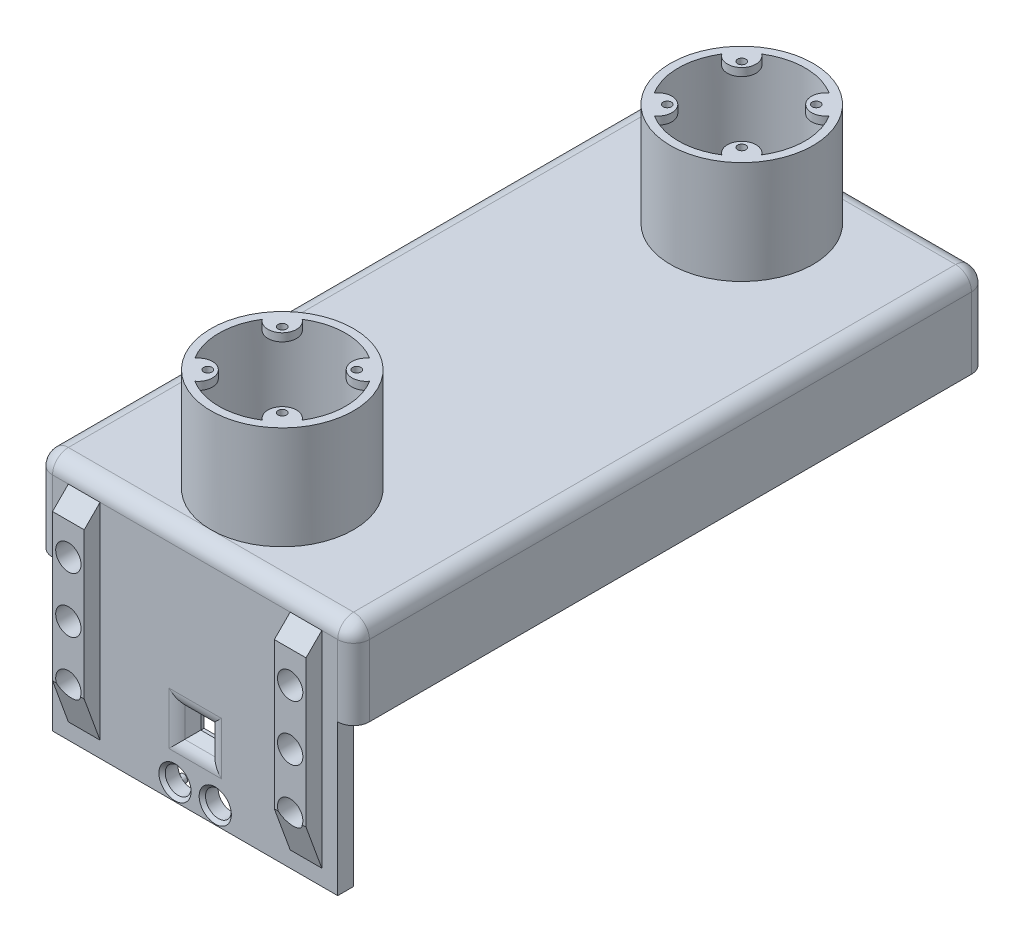
SolidWorks part; units mm, degrees
ref_plane "Front Plane" through (0, 0, 0) normal (0, 0, 1) x (1, 0, 0)
ref_plane "Top Plane" through (0, 0, 0) normal (0, 1, 0) x (1, 0, 0)
ref_plane "Right Plane" through (0, 0, 0) normal (1, 0, 0) x (0, 0, -1)
sketch "Sketch1" plane through (0, 0, 0) normal (0, 0, 1) x (1, 0, 0)
  line L1 (-90, -75) -> (90, -75)
  line L2 (-90, -75) -> (-90, 75)
  line L3 (-90, 75) -> (90, 75)
  line L4 (90, -75) -> (90, 75)
  line L5 (-90, -75) -> (90, 75) construction
  line L6 (-90, 75) -> (90, -75) construction
  point P0 (0, 0)
  dimension "D1" = 150
  dimension "D2" = 180
extrude "Boss-Extrude1" add sketch "Sketch1" along normal blind 10
sketch "Sketch2" plane through (0, 0, 10) normal (0, 0, 1) x (1, 0, 0)
  line L0 (0, 0) -> (0, 75) construction
  line L1 (90, 75) -> (-90, 75) construction
  line L2 (0, 0) -> (-70, 0) construction
  line L3 (80, 65) -> (60, 65)
  line L4 (-80, -65) -> (-60, -65)
  line L5 (-80, -65) -> (-80, 65)
  line L6 (-80, 65) -> (-60, 65)
  line L7 (-60, -65) -> (-60, 65)
  line L8 (-80, -65) -> (-60, 65) construction
  line L9 (-80, 65) -> (-60, -65) construction
  line L10 (60, -65) -> (60, 65)
  line L11 (80, -65) -> (60, -65)
  line L12 (80, -65) -> (80, 65)
  dimension "D1" = 130
  dimension "D2" = 20
extrude "Boss-Extrude2" add sketch "Sketch2" along normal blind 10
sketch "Sketch3" plane through (0, 0, 20) normal (0, 0, 1) x (1, 0, 0)
  line L0 (-70, 65) -> (-70, -65) construction
  line L1 (-60, 65) -> (-80, 65) construction
  line L2 (-80, -65) -> (-60, -65) construction
  line L3 (-70, 0) -> (-70, -35) construction
  line L4 (-70, 0) -> (-70, 35) construction
  line L5 (0, 0) -> (0, 46.7529) construction
  circle A0 centre (-70, 0) radius 8
  circle A1 centre (-70, -35) radius 8
  circle A2 centre (-70, 35) radius 8
  circle A3 centre (70, -35) radius 8
  circle A4 centre (70, 0) radius 8
  circle A5 centre (70, 35) radius 8
extrude "Cut-Extrude1" cut sketch "Sketch3" against normal up to next
chamfer "Chamfer1" distance 10 angle 45 2 edges at (70, 65, 20) (-70, 65, 20)
chamfer "Chamfer2" distance 10 angle 70 2 edges at (70, -65, 20) (-70, -65, 20) first distance on face at (70, -65, 15) first distance on face at (-70, -65, 15)
sketch "Sketch5" plane through (0, 75, 0) normal (0, 1, 0) x (1, 0, 0)
  line L1 (100, -10) -> (-100, -10)
  line L3 (100, 390) -> (-100, 390)
  line L4 (-100, -10) -> (-100, 390)
  line L5 (100, -10) -> (100, 390)
  dimension "D2" = 400
extrude "Boss-Extrude4" add sketch "Sketch5" against normal blind 10
sketch "Sketch6" plane through (0, 0, -390) normal (0, 0, -1) x (-1, 0, 0)
  line L1 (-100, 75) -> (100, 75)
  line L2 (-100, 75) -> (-100, 20)
  line L3 (-100, 20) -> (100, 20)
  line L4 (100, 75) -> (100, 20)
  dimension "D1" = 200
  dimension "D2" = 55
extrude "Boss-Extrude5" add sketch "Sketch6" against normal blind 10
sketch "Sketch7" plane through (0, 65, 0) normal (0, -1, 0) x (1, 0, 0)
  line L0 (100, -390) -> (-100, -390) construction
  line L1 (-100, 10) -> (-90, 10)
  line L2 (-100, 10) -> (-100, -390)
  line L3 (-100, -390) -> (-90, -390)
  line L4 (-90, 10) -> (-90, -390)
  line L5 (-90, 10) -> (90, 10) construction
  line L6 (100, -390) -> (90, -390)
  line L7 (100, -390) -> (100, 10)
  line L8 (100, 10) -> (90, 10)
  line L9 (90, -390) -> (90, 10)
extrude "Boss-Extrude6" add sketch "Sketch7" along normal blind 45
fillet "Fillet1" radius 10 8 edges at (-100, 75, -190) (100, 75, -190) (0, 75, -390) (0, 75, 10) (100, 47.5, 10) (100, 47.5, -390) (-100, 47.5, -390) (-100, 47.5, 10)
sketch "Sketch8" plane through (0, 75, 0) normal (0, 1, 0) x (1, 0, 0)
  line L0 (-90, 190) -> (90, 190) construction
  line L1 (-90, 380) -> (-90, 0) construction
  line L2 (90, 0) -> (90, 380) construction
  line L3 (0, 390) -> (0, 335) construction
  line L4 (-100, -10) -> (100, -10) construction
  line L5 (-100, -10) -> (-100, 390) construction
  line L6 (-100, 390) -> (100, 390) construction
  line L7 (100, -10) -> (100, 390) construction
  line L8 (-100, -10) -> (100, 390) construction
  line L9 (-100, 390) -> (100, -10) construction
  line L10 (-100, 65) -> (100, 65) construction
  line L11 (-100, 65) -> (-100, 315) construction
  line L12 (-100, 315) -> (100, 315) construction
  line L13 (100, 65) -> (100, 315) construction
  line L14 (-100, 65) -> (100, 315) construction
  line L15 (-100, 315) -> (100, 65) construction
  line L16 (0, -10) -> (0, 45) construction
  circle A2 centre (0, 335) radius 40
  circle A3 centre (0, 45) radius 40
  point P6 (0, 190)
  point P11 (0, 190)
  dimension "D1" = 250
sketch "Sketch9" plane through (0, 75, 0) normal (0, 1, 0) x (1, 0, 0)
  line L0 (0, -10) -> (0, 45) construction
  line L1 (0, 390) -> (0, 335) construction
  line L2 (0, -10) -> (0, 45) construction
  line L3 (0, 390) -> (0, 335) construction
  circle A0 centre (0, 45) radius 40 construction
  circle A1 centre (0, 335) radius 40 construction
  circle A2 centre (0, 45) radius 40
  circle A3 centre (0, 335) radius 40
extrude "Cut-Extrude2" cut sketch "Sketch9" against normal blind 10
sketch "Sketch10" plane through (-90, 0, 0) normal (1, 0, 0) x (0, 0, -1)
  line L0 (0, 65) -> (0, 20) construction
  line L1 (380, 20) -> (0, 20)
  line L2 (380, 20) -> (380, 30)
  line L3 (380, 30) -> (0, 30)
  line L4 (0, 20) -> (0, 30)
  dimension "D1" = 10
extrude "Boss-Extrude7" add sketch "Sketch10" along normal blind 180
sketch "Sketch11" plane through (0, 20, 0) normal (0, -1, 0) x (1, 0, 0)
  line L2 (0, -45) -> (0, -90) construction
  line L3 (0, -335) -> (0, -290) construction
  line L5 (-100, 10) -> (-100, -390) construction
  line L6 (100, 10) -> (100, -390) construction
  line L8 (100, -90) -> (-100, -90)
  line L11 (-90, 0) -> (-60, 0)
  line L12 (-90, 0) -> (-90, -20)
  line L13 (-90, -20) -> (-60, -20)
  line L14 (-60, 0) -> (-60, -20)
  line L15 (90, -20) -> (60, -20)
  line L16 (60, 0) -> (60, -20)
  line L17 (90, 0) -> (60, 0)
  line L18 (90, 0) -> (90, -20)
  line L20 (-90, -290) -> (90, -290)
  line L21 (-90, -290) -> (-90, -90)
  line L22 (-90, -90) -> (90, -90)
  line L23 (90, -290) -> (90, -90)
  line L24 (-90, -290) -> (90, -90) construction
  line L25 (-90, -90) -> (90, -290) construction
  circle A0 centre (0, -45) radius 40 construction
  circle A1 centre (0, -335) radius 40 construction
  point P26 (0, -190)
  line M12 (90, 0) -> (-90, 0)
  dimension "D1" = 20
  dimension "D2" = 30
extrude "Cut-Extrude5" cut sketch "Sketch11" against normal blind 10 contours L20 L23 L8 L21 | L14 L12 L13 M12 | L18 L16 L15 M12 region at (0, 20, -190) region at (75, 20, -10) region at (-75, 20, -10)
sketch "Sketch13" plane through (0, 75, 0) normal (0, 1, 0) x (1, 0, 0)
  line L0 (-90, 190) -> (90, 190) construction
  circle A0 centre (0, 45) radius 40
  circle A1 centre (0, 45) radius 45
  circle A2 centre (0, 335) radius 40
  circle A3 centre (0, 335) radius 45
extrude "Boss-Extrude8" add sketch "Sketch13" along normal blind 60
sketch "Sketch14" plane through (0, 135, 0) normal (0, 1, 0) x (1, 0, 0)
  line L0 (0, 335) -> (0, 358.5) construction
  line L1 (0, 390) -> (0, 335) construction
  line L2 (0, 358.5) -> (-23.5, 358.5) construction
  line L3 (0, 335) -> (-25.7533, 335) construction
  line L4 (100, 190) -> (-100, 190) construction
  line L5 (100, -10) -> (100, 390) construction
  line L6 (-100, -10) -> (-100, 390) construction
  line L7 (-23.5, 358.5) -> (-23.5, 366.0195) construction
  line L8 (-23.5, 358.5) -> (-26.5406, 361.5406) construction
  circle A2 centre (-23.5, 358.5) radius 2.6
  circle A3 centre (23.5, 358.5) radius 2.6
  circle A4 centre (23.5, 311.5) radius 2.6
  circle A5 centre (-23.5, 311.5) radius 2.6
  circle A6 centre (-23.5, 68.5) radius 2.6
  circle A7 centre (23.5, 68.5) radius 2.6
  circle A8 centre (23.5, 21.5) radius 2.6
  circle A9 centre (-23.5, 21.5) radius 2.6
  arc A10 (-33.8573, 356.2998) -> (-21.2998, 368.8573) centre (-26.5406, 361.5406) ccw
  circle A11 centre (0, 335) radius 45
  arc A12 (-33.8573, 356.2998) -> (-33.8573, 313.7002) centre (0, 335) ccw
  arc A13 (33.8573, 356.2998) -> (21.2998, 368.8573) centre (26.5406, 361.5406) cw
  arc A14 (-33.8573, 313.7002) -> (-21.2998, 301.1427) centre (-26.5406, 308.4594) cw
  arc A15 (33.8573, 313.7002) -> (21.2998, 301.1427) centre (26.5406, 308.4594) ccw
  circle A16 centre (0, 45) radius 45
  arc A17 (-33.8573, 23.7002) -> (-33.8573, 66.2998) centre (0, 45) cw
  arc A18 (-33.8573, 66.2998) -> (-21.2998, 78.8573) centre (-26.5406, 71.5406) ccw
  arc A19 (33.8573, 66.2998) -> (21.2998, 78.8573) centre (26.5406, 71.5406) cw
  arc A20 (33.8573, 23.7002) -> (21.2998, 11.1427) centre (26.5406, 18.4594) ccw
  arc A21 (-33.8573, 23.7002) -> (-21.2998, 11.1427) centre (-26.5406, 18.4594) cw
  arc A22 (-21.2998, 78.8573) -> (21.2998, 78.8573) centre (0, 45) cw
  arc A23 (33.8573, 66.2998) -> (33.8573, 23.7002) centre (0, 45) cw
  arc A24 (21.2998, 11.1427) -> (-21.2998, 11.1427) centre (0, 45) cw
  arc A25 (33.8573, 313.7002) -> (33.8573, 356.2998) centre (0, 335) ccw
  arc A26 (-21.2998, 301.1427) -> (21.2998, 301.1427) centre (0, 335) ccw
  arc A27 (21.2998, 368.8573) -> (-21.2998, 368.8573) centre (0, 335) ccw
  dimension "D1" = 45
  dimension "D2" = 4.3
extrude "Boss-Extrude9" add sketch "Sketch14" along normal blind 5
sketch "Sketch15" plane through (-100, 0, 0) normal (-1, 0, 0) x (0, 0, 1)
  line L0 (-190, 75) -> (-190, 275) construction
sketch "Sketch16" plane through (0, 140, 0) normal (0, 1, 0) x (1, 0, 0)
  line L0 (0, 290) -> (0, 90) construction
  circle A0 centre (0, 335) radius 45 construction
  circle A1 centre (0, 335) radius 45 construction
  circle A2 centre (0, 45) radius 45 construction
  circle A3 centre (0, 45) radius 45 construction
sketch "Sketch17" plane through (0, 0, 0) normal (0, 0, -1) x (-1, 0, 0)
  line L0 (0, -75) -> (0, -64.35) construction
  line L1 (90, -75) -> (-90, -75) construction
  line L3 (-22.85, -53.7) -> (22.85, -53.7) construction
  line L4 (-22.85, -53.7) -> (-22.85, -75) construction
  line L5 (-22.85, -75) -> (22.85, -75) construction
  line L6 (22.85, -53.7) -> (22.85, -75) construction
  line L7 (-22.85, -53.7) -> (22.85, -75) construction
  line L8 (-22.85, -75) -> (22.85, -53.7) construction
  circle A0 centre (-20.35, -56.2) radius 1.5
  circle A1 centre (20.35, -72.5) radius 1.5
  circle A2 centre (-20.35, -56.2) radius 2.5
  circle A3 centre (20.35, -72.5) radius 2.5
  dimension "D1" = 2.5
  dimension "D3" = 3
  dimension "D6" = 3
  dimension "D2" = 2.5
  dimension "D4" = 2.5
  dimension "D5" = 2.5
extrude "Boss-Extrude10" add sketch "Sketch17" along normal blind 3
sketch "Sketch18" plane through (0, 0, 0) normal (0, 0, -1) x (-1, 0, 0)
  line L0 (0, -75) -> (0, -53.7) construction
  line L1 (20.35, -75) -> (-90, -75) construction
  line L3 (0, -64.35) -> (-20.85, -64.35) construction
  circle A0 centre (-12.7, -64.35) radius 8.15
  circle A1 centre (12.7, -64.35) radius 8.15
  point P10 (0, 0)
  dimension "D1" = 20.85
extrude "Cut-Extrude6" cut sketch "Sketch18" against normal through all
chamfer "Chamfer3" distance 2 angle 45 2 edges at (4.55, -64.35, 10) (-20.85, -64.35, 10)
sketch "Sketch19" plane through (0, 0, 10) normal (0, 0, 1) x (1, 0, 0)
  line L0 (0, -75) -> (0, -45) construction
  line L1 (-90, -75) -> (90, -75) construction
  line L2 (0, -45) -> (0, -21) construction
  line L3 (-10.5, -43.2) -> (-10.5, -37.05) construction
  line L4 (-12.6, -45) -> (12.6, -45)
  line L5 (-12.6, -45) -> (-12.6, -21)
  line L6 (-12.6, -21) -> (12.6, -21) construction
  line L7 (12.6, -45) -> (12.6, -21)
  line L8 (-12.6, -45) -> (12.6, -21) construction
  line L9 (-12.6, -21) -> (12.6, -45) construction
  line L10 (-10.5, -37.05) -> (3.3057, -37.05) construction
  circle A1 centre (-10.5, -43.2) radius 1.05
  circle A2 centre (10.5, -43.2) radius 1.05
  circle A7 centre (10.5, -43.2) radius 1.8
  circle A8 centre (-10.5, -43.2) radius 1.8
  circle A9 centre (10.5, -30.9) radius 1.05
  circle A10 centre (10.5, -30.9) radius 1.8
  circle A11 centre (-10.5, -30.9) radius 1.05
  circle A12 centre (-10.5, -30.9) radius 1.8
  point P5 (0, -33)
  dimension "D1" = 1.8
  dimension "D2" = 21
sketch "Sketch20" plane through (0, 0, 0) normal (0, 0, -1) x (-1, 0, 0)
  line L0 (-12.6, -45) -> (-12.6, -21) construction
  line L1 (12.6, -45) -> (-12.6, -45) construction
  line L2 (12.6, -45) -> (12.6, -21) construction
  line L3 (-12.6, -45) -> (-12.6, -21)
  line L4 (12.6, -45) -> (-12.6, -45)
  line L5 (12.6, -45) -> (12.6, -21)
  circle A1 centre (-10.5, -43.2) radius 1.05
  circle A2 centre (-10.5, -43.2) radius 1.05
  circle A3 centre (10.5, -43.2) radius 1.05
  circle A4 centre (10.5, -43.2) radius 1.05
  circle A5 centre (10.5, -30.9) radius 1.8
  circle A6 centre (10.5, -30.9) radius 1.8
  circle A7 centre (10.5, -30.9) radius 1.05
  circle A8 centre (10.5, -30.9) radius 1.05
  circle A9 centre (-10.5, -30.9) radius 1.8
  circle A10 centre (-10.5, -30.9) radius 1.8
  circle A11 centre (-10.5, -30.9) radius 1.05
  circle A12 centre (-10.5, -30.9) radius 1.05
  circle A13 centre (10.5, -43.2) radius 1.8
  circle A14 centre (10.5, -43.2) radius 1.8
  circle A15 centre (-10.5, -43.2) radius 1.8
  circle A16 centre (-10.5, -43.2) radius 1.8
  dimension "D1" = 0
  dimension "D2" = 0
  dimension "D3" = 0
  dimension "D4" = 0
  dimension "D5" = 0
  dimension "D6" = 0
  dimension "D7" = 0
  dimension "D8" = 0
extrude "Boss-Extrude11" add sketch "Sketch20" along normal blind 2 contours A10 A12 | A6 A8 | A14 A4 | A16 A2 region at (11.7368, -41.9632, 0) region at (-9.2632, -41.9632, 0) region at (-8.7509, -30.9, 0) region at (12.2491, -30.9, 0)
sketch "Sketch21" plane through (0, 0, 0) normal (0, 0, -1) x (-1, 0, 0)
  line L0 (0, -26.9) -> (0, -31.3) construction
  line L1 (-12.6, -45) -> (-12.6, -21) construction
  line L2 (-12.6, -21) -> (0, -21) construction
  line L3 (0, -21) -> (0, -26.9) construction
  line L5 (-4.4, -35.7) -> (4.4, -35.7)
  line L6 (-4.4, -35.7) -> (-4.4, -26.9)
  line L7 (-4.4, -26.9) -> (4.4, -26.9)
  line L8 (4.4, -35.7) -> (4.4, -26.9)
  line L9 (-4.4, -35.7) -> (4.4, -26.9) construction
  line L10 (-4.4, -26.9) -> (4.4, -35.7) construction
  dimension "D1" = 4.4
  dimension "D2" = 5.9
extrude "Cut-Extrude7" cut sketch "Sketch21" against normal through all contours L6 L5 L8 L7
chamfer "Chamfer4" distance 8 angle 45 4 edges at (0, -35.7, 10) (-4.4, -31.3, 10) (4.4, -31.3, 10) (0, -26.9, 10)
fillet "Fillet2" radius 10 4 edges at (0, -43.7, 10) (-12.4, -31.3, 10) (12.4, -31.3, 10) (0, -18.9, 10)
sketch "Sketch22" plane through (0, 20, 0) normal (0, -1, 0) x (1, 0, 0)
  line L1 (-90, 0) -> (90, 0)
  line L2 (-90, 0) -> (-90, -380)
  line L3 (-90, -380) -> (90, -380)
  line L4 (90, 0) -> (90, -380)
extrude "Cut-Extrude8" cut sketch "Sketch22" against normal blind 10
